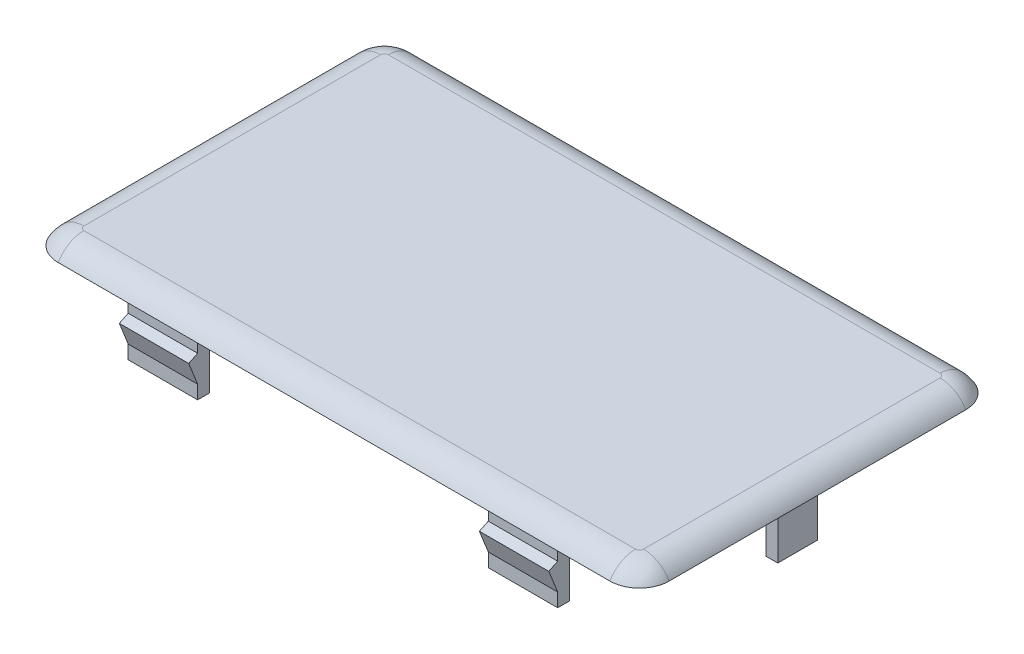
SolidWorks part; units mm, degrees
ref_plane "Front Plane" through (0, 0, 0) normal (0, 0, 1) x (1, 0, 0)
ref_plane "Top Plane" through (0, 0, 0) normal (0, 1, 0) x (1, 0, 0)
ref_plane "Right Plane" through (0, 0, 0) normal (1, 0, 0) x (0, 0, -1)
sketch "Sketch1" plane through (0, 0, 0) normal (0, 1, 0) x (1, 0, 0)
  line L1 (-46.5, 30) -> (46.5, 30)
  line L2 (-51.5, 25) -> (-51.5, -25)
  line L3 (-46.5, -30) -> (46.5, -30)
  line L4 (51.5, 25) -> (51.5, -25)
  line L5 (-51.5, 30) -> (51.5, -30) construction
  line L6 (-51.5, -30) -> (51.5, 30) construction
  arc A0 (46.5, -30) -> (51.5, -25) centre (46.5, -25) ccw
  arc A1 (51.5, 25) -> (46.5, 30) centre (46.5, 25) ccw
  arc A2 (-46.5, -30) -> (-51.5, -25) centre (-46.5, -25) cw
  arc A3 (-46.5, 30) -> (-51.5, 25) centre (-46.5, 25) ccw
  point P0 (0, 0)
  dimension "D3" = 5
  dimension "D1" = 103
  dimension "D2" = 60
extrude "Boss-Extrude1" add sketch "Sketch1" along normal blind 2.5
fillet "Fillet1" radius 5 8 edges at (-50.0355, 2.5, -28.5355) (0, 2.5, -30) (50.0355, 2.5, -28.5355) (51.5, 2.5, 0) (50.0355, 2.5, 28.5355) (0, 2.5, 30) (-50.0355, 2.5, 28.5355) (-51.5, 2.5, 0)
sketch "Sketch2" plane through (0, 0, 0) normal (0, -1, 0) x (1, 0, 0)
  line L0 (0, 30) -> (0, -30) construction
  line L1 (-36.2, 28.5) -> (-24.5, 28.5)
  line L2 (-36.2, 28.5) -> (-36.2, 26.5)
  line L3 (-36.2, 26.5) -> (-31.35, 26.5)
  line L4 (-24.5, 28.5) -> (-24.5, 26.5)
  line L5 (-46.5, 30) -> (46.5, 30) construction
  line L6 (46.5, -30) -> (-46.5, -30) construction
  line L7 (-51.5, 0) -> (51.5, 0) construction
  line L8 (-51.5, -25) -> (-51.5, 25) construction
  line L9 (51.5, 25) -> (51.5, -25) construction
  line L10 (48.225, -3.2828) -> (46.225, -3.2828)
  line L11 (24.5, 28.5) -> (36.2, 28.5)
  line L12 (24.5, 28.5) -> (24.5, 26.5)
  line L13 (24.5, 26.5) -> (29.35, 26.5)
  line L14 (36.2, 28.5) -> (36.2, 26.5)
  line L15 (24.5, -26.5) -> (29.35, -26.5)
  line L16 (24.5, -26.5) -> (24.5, -28.5)
  line L17 (24.5, -28.5) -> (36.2, -28.5)
  line L18 (36.2, -26.5) -> (36.2, -28.5)
  line L19 (-36.2, -28.5) -> (-24.5, -28.5)
  line L20 (-36.2, -28.5) -> (-36.2, -26.5)
  line L21 (-36.2, -26.5) -> (-31.35, -26.5)
  line L22 (-24.5, -28.5) -> (-24.5, -26.5)
  line L23 (-48.225, 3.4172) -> (-46.225, 3.4172)
  line L24 (-48.225, 3.4172) -> (-48.225, -3.2828)
  line L25 (-48.225, -3.2828) -> (-46.225, -3.2828)
  line L26 (-46.225, 3.4172) -> (-46.225, 1)
  line L27 (46.225, 3.4172) -> (46.225, 1)
  line L28 (48.225, 3.4172) -> (46.225, 3.4172)
  line L29 (48.225, 3.4172) -> (48.225, -3.2828)
  line L30 (-46.225, -0.9998) -> (-46.225, -3.2828)
  line L31 (-46.225, 1) -> (-40.225, 1)
  line L33 (-46.225, -0.9998) -> (-40.225, -0.9998)
  line L34 (-40.225, 1) -> (-40.225, -0.9998)
  line L35 (40.225, 1) -> (40.225, -0.9998)
  line L36 (46.225, 1) -> (40.225, 1)
  line L37 (46.225, -0.9998) -> (40.225, -0.9998)
  line L38 (46.225, -0.9998) -> (46.225, -3.2828)
  line L39 (-30.35, 28.5) -> (-30.35, -31.9661) construction
  line L40 (30.35, 28.5) -> (30.35, -35.5794) construction
  line L41 (-29.35, 26.5) -> (-24.5, 26.5)
  line L43 (-31.35, 26.5) -> (-31.35, 20.5)
  line L44 (-31.35, 20.5) -> (-29.35, 20.5)
  line L45 (-29.35, 26.5) -> (-29.35, 20.5)
  line L46 (-29.35, -26.5) -> (-24.5, -26.5)
  line L48 (-31.35, -26.5) -> (-31.35, -20.5)
  line L49 (-31.35, -20.5) -> (-29.35, -20.5)
  line L50 (-29.35, -26.5) -> (-29.35, -20.5)
  line L51 (31.35, -26.5) -> (36.2, -26.5)
  line L53 (29.35, 26.5) -> (29.35, 20.5)
  line L54 (29.35, 20.5) -> (31.35, 20.5)
  line L55 (31.35, 26.5) -> (31.35, 20.5)
  line L57 (29.35, -26.5) -> (29.35, -20.5)
  line L58 (29.35, -20.5) -> (31.35, -20.5)
  line L59 (31.35, -26.5) -> (31.35, -20.5)
  line L60 (31.35, 26.5) -> (36.2, 26.5)
  dimension "D1" = 2
  dimension "D2" = 11.7
  dimension "D3" = 2
  dimension "D4" = 11.7
  dimension "D5" = 49
  dimension "D6" = 24.5
  dimension "D7" = 24.5
  dimension "D8" = 15.3
  dimension "D9" = 2
  dimension "D11" = 26.5
  dimension "D12" = 2
  dimension "D13" = 11.7
  dimension "D14" = 49
  dimension "D15" = 24.5
  dimension "D16" = 2
  dimension "D17" = 6.7
  dimension "D18" = 46.225
  dimension "D19" = 6
  dimension "D20" = 1.9998
  dimension "D21" = 1
  dimension "D22" = 6
  dimension "D23" = 1
  dimension "D24" = 2
  dimension "D25" = 6
  dimension "D26" = 2
  dimension "D27" = 1
  dimension "D28" = 6
  dimension "D29" = 2
  dimension "D30" = 1
  dimension "D31" = 2
  dimension "D32" = 1
  dimension "D33" = 6
extrude "Boss-Extrude2" add sketch "Sketch2" along normal blind 9.8
sketch "Sketch4" plane through (0, 0, -0.9998) normal (0, 0, -1) x (-1, 0, 0)
  line L0 (40.225, 0) -> (46.225, -9.8)
  line L1 (46.225, -9.8) -> (40.225, -9.8)
  line L2 (40.225, -9.8) -> (40.225, 0)
extrude "Cut-Extrude1" cut sketch "Sketch4" against normal blind 9.8
mirror "Mirror1" about plane through (0, 0, 0) normal (1, 0, 0) of "Cut-Extrude1"
sketch "Sketch5" plane through (-31.35, 0, 0) normal (-1, 0, 0) x (0, 0, 1)
  line L0 (-26.5, -9.8) -> (-20.5, 0)
  line L1 (-20.5, 0) -> (-20.5, -9.8)
  line L2 (-20.5, -9.8) -> (-26.5, -9.8)
extrude "Cut-Extrude2" cut sketch "Sketch5" against normal through all
mirror "Mirror2" about plane through (0, 0, 0) normal (0, 0, 1) of "Cut-Extrude2"
sketch "Sketch6" plane through (36.2, 0, 0) normal (1, 0, 0) x (0, 0, -1)
  line L0 (-28.5, -3) -> (-28.5, -7.5)
  line L1 (-28.5, -9.8) -> (-28.5, 0) construction
  line L2 (-28.5, -3) -> (-30, -3.7261)
  line L3 (-30, -3.7261) -> (-28.5, -7.5)
  dimension "D1" = 4.5
  dimension "D2" = 1.5
  dimension "D3" = 3
extrude "Boss-Extrude3" add sketch "Sketch6" against normal blind 11.7
mirror "Mirror3" about plane through (0, 0, 0) normal (1, 0, 0) of "Boss-Extrude3"
mirror "Mirror4" about plane through (0, 0, 0) normal (0, 0, 1) of "Mirror3"
